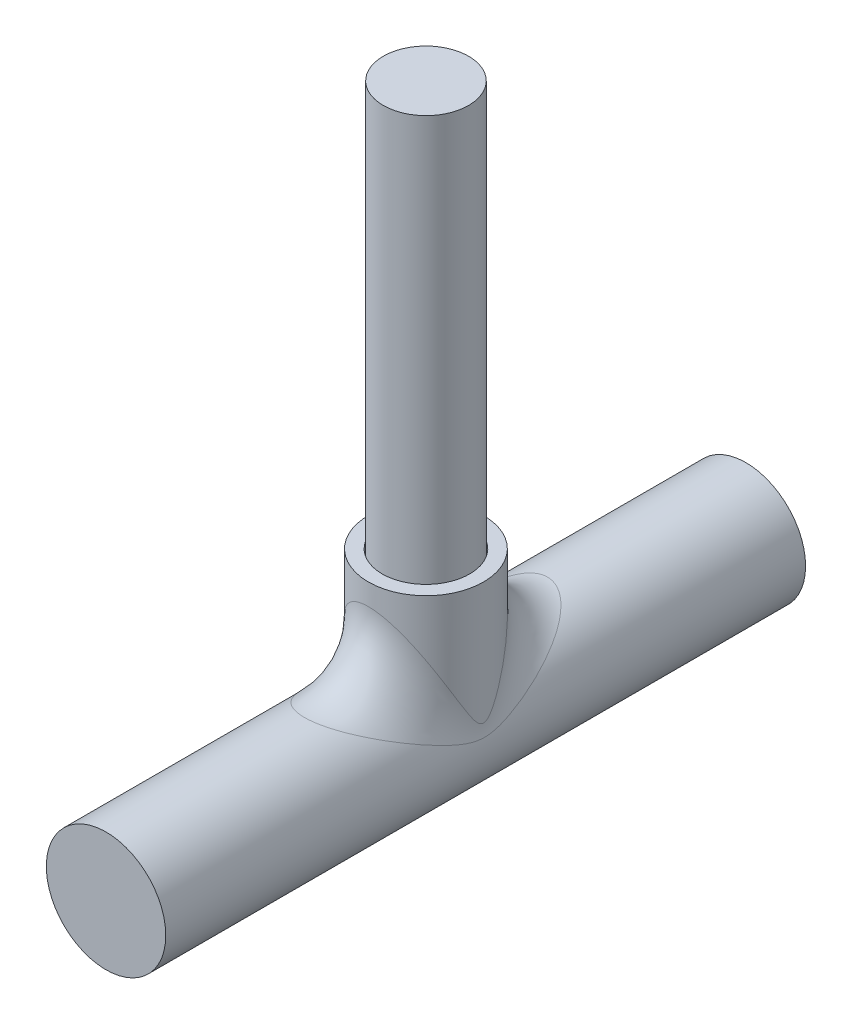
SolidWorks part; units mm, degrees
ref_plane "Front Plane" through (0, 0, 0) normal (0, 0, 1) x (1, 0, 0)
ref_plane "Top Plane" through (0, 0, 0) normal (0, 1, 0) x (1, 0, 0)
ref_plane "Right Plane" through (0, 0, 0) normal (1, 0, 0) x (0, 0, -1)
sketch "Sketch1" plane through (0, 0, 0) normal (0, 0, 1) x (1, 0, 0)
  line L0 (0, 0) -> (0, 14) construction
  circle A0 centre (0, 0) radius 14
  dimension "D1" = 28
extrude "Boss-Extrude1" add sketch "Sketch1" along normal mid plane 150
sketch "Sketch4" plane through (0, 0, -75) normal (0, 0, -1) x (-1, 0, 0)
  line L0 (0, 0) -> (0, 14) construction
  circle A0 centre (0, 0) radius 14 construction
ref_plane "Plane1" through (0, 14, 0) normal (0, 1, 0) x (1, 0, 0)
sketch "Sketch2" plane through (0, 14, 0) normal (0, 1, 0) x (1, 0, 0)
  circle A2 centre (0, 0) radius 13.5
  dimension "D1" = 27
extrude "Boss-Extrude3" add sketch "Sketch2" along normal blind 20 and the other way up to body separate body
fillet "Fillet1" radius 15 1 edges at (1.1285, 13.9544, 13.4528)
sketch "Sketch5" plane through (0, 34, 0) normal (0, 1, 0) x (1, 0, 0)
  circle A0 centre (0, 0) radius 10.25
  dimension "D1" = 20.5
extrude "Cut-Extrude1" cut sketch "Sketch5" against normal blind 35
sketch "Sketch6" plane through (0, -1, 0) normal (0, 1, 0) x (1, 0, 0)
  circle A0 centre (0, 0) radius 10
  dimension "D1" = 20
extrude "TIL ASSEMBLY - SLETT" add sketch "Sketch6" along normal blind 130
